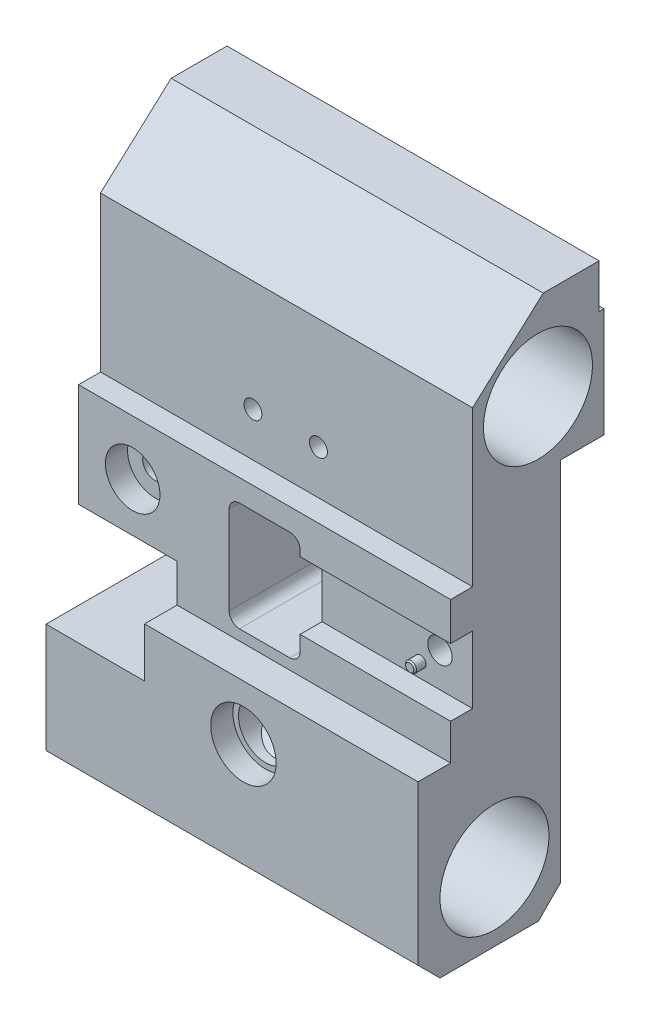
SolidWorks part; units mm, degrees
material "1060 Alloy"
ref_plane "Front Plane" through (0, 0, 0) normal (0, 0, 1) x (1, 0, 0)
ref_plane "Top Plane" through (0, 0, 0) normal (0, 1, 0) x (1, 0, 0)
ref_plane "Right Plane" through (0, 0, 0) normal (1, 0, 0) x (0, 0, -1)
sketch "Sketch1" plane through (0, 0, 0) normal (1, 0, 0) x (0, 0, -1)
  line L0 (14.15, 137.2) -> (30.37, 137.2)
  line L1 (30.37, 137.2) -> (30.37, 124.41)
  line L2 (30.37, 124.41) -> (31.79, 124.41)
  line L3 (31.79, 124.41) -> (31.79, 92.72)
  line L4 (31.79, 92.72) -> (19.1, 92.72)
  line L5 (19.1, 92.72) -> (19.1, -13.636)
  line L6 (19.1, -13.636) -> (12.736, -20)
  line L7 (12.736, -20) -> (-15.816, -20)
  line L8 (-15.816, -20) -> (-22.18, -13.636)
  line L9 (-22.18, -13.636) -> (-22.18, 32.5)
  line L10 (-22.18, 32.5) -> (-12.73, 32.5)
  line L11 (-12.73, 32.5) -> (-12.73, 73.61)
  line L12 (-12.73, 73.61) -> (-6.36, 73.61)
  line L13 (-6.36, 73.61) -> (-6.36, 118.61)
  line L14 (-6.36, 118.61) -> (14.15, 137.2)
  line L15 (-22.18, 32.5) -> (-22.18, 137.2) construction
  line L16 (-22.18, 137.2) -> (14.15, 137.2) construction
  line L17 (30.37, 137.2) -> (31.79, 137.2) construction
  line L18 (31.79, 137.2) -> (31.79, 124.41) construction
  line L19 (31.79, 92.72) -> (31.79, -20) construction
  line L20 (31.79, -20) -> (12.736, -20) construction
  line L21 (-22.18, -13.636) -> (-22.18, -20) construction
  line L22 (-22.18, -20) -> (-15.816, -20) construction
  line L23 (-22.18, 0) -> (31.79, 0) construction
  line L24 (0, -20) -> (0, 17.0401) construction
  line L25 (-22.18, -13.636) -> (19.1, -13.636) construction
  line L26 (0, -15.83) -> (46.0148, -15.83) construction
  line L27 (15.83, 0) -> (15.83, 26.825) construction
  line L28 (0, 15.83) -> (31.79, 15.83) construction
  line L29 (12.625, 111.985) -> (46.8932, 111.985) construction
  line L30 (12.625, 127.815) -> (56.5516, 127.815) construction
  line L31 (12.625, 96.155) -> (52.1782, 96.155) construction
  line L32 (30.37, 124.41) -> (30.37, 97.4751) construction
  line L33 (-15.83, 0) -> (-15.83, 21.2691) construction
  circle A0 centre (0, 0) radius 15.83
  circle A1 centre (12.625, 111.985) radius 15.83
  dimension "D19" = 111.985
  dimension "D14" = 31.66
  dimension "D1" = 41.28
  dimension "D2" = 38.15
  dimension "D3" = 157.2
  dimension "D4" = 44.48
  dimension "D5" = 1.42
  dimension "D6" = 31.69
  dimension "D7" = 25.46
  dimension "D8" = 31.83
  dimension "D9" = 52.5
  dimension "D10" = 93.61
  dimension "D11" = 9
  dimension "D12" = 12.625
  dimension "D13" = 16.22
  dimension "D15" = 45
  dimension "D16" = 3.27
  dimension "D17" = 6.35
  dimension "D18" = 4.17
extrude "Boss-Extrude1" add sketch "Sketch1" along normal blind 54 and the other way blind 54
sketch "Sketch2" plane through (0, 0, -19.1) normal (0, 0, -1) x (-1, 0, 0)
  line L0 (54, -13.636) -> (54, 92.72) construction
  line L1 (-7.3, 67.2) -> (7.3, 67.2)
  line L2 (-10.3, 64.2) -> (-10.3, 38.6)
  line L3 (-7.3, 35.6) -> (7.3, 35.6)
  line L4 (10.3, 64.2) -> (10.3, 38.6)
  line L5 (54, 43.53) -> (25.4, 43.53)
  line L6 (54, 43.53) -> (54, 18.13)
  line L7 (54, 18.13) -> (25.4, 18.13)
  line L8 (25.4, 43.53) -> (25.4, 18.13)
  line L9 (-9.25, 86.37) -> (9.75, 86.37) construction
  line L10 (-10.3, 64.2) -> (-10.3, 67.2) construction
  line L11 (-10.3, 67.2) -> (-7.3, 67.2) construction
  line L12 (7.3, 67.2) -> (10.3, 67.2) construction
  line L13 (10.3, 67.2) -> (10.3, 64.2) construction
  line L14 (10.3, 38.6) -> (10.3, 35.6) construction
  line L15 (10.3, 35.6) -> (7.3, 35.6) construction
  line L16 (-7.3, 35.6) -> (-10.3, 35.6) construction
  line L17 (-10.3, 35.6) -> (-10.3, 38.6) construction
  line L18 (-54, -13.636) -> (-54, 92.72) construction
  line L19 (54, -20) -> (-54, -20) construction
  line L21 (54, 137.2) -> (-54, 137.2) construction
  line L22 (-3.3, 16.595) -> (-3.3, 92.72) construction
  line L25 (54, 92.72) -> (-54, 92.72) construction
  line L26 (9.75, 86.37) -> (9.75, 92.72) construction
  line L27 (-9.25, 86.37) -> (-9.25, 92.72) construction
  line L28 (38.3, 57.72) -> (38.3, 92.72) construction
  line L29 (-44.55, 52.92) -> (-44.55, 92.72) construction
  circle A0 centre (-3.3, 16.595) radius 7.875
  circle A1 centre (-44.55, 52.92) radius 5.5 construction
  circle A2 centre (38.3, 57.72) radius 5.55 construction
  circle A3 centre (-9.25, 86.37) radius 2.6
  circle A4 centre (9.75, 86.37) radius 2.6
  circle A5 centre (-3.3, 16.595) radius 9.42 construction
  circle A6 centre (-9.25, 86.37) radius 4.425 construction
  circle A7 centre (9.75, 86.37) radius 4.425 construction
  circle A8 centre (38.3, 57.72) radius 3.525
  circle A9 centre (-44.55, 52.92) radius 3.55
  arc A10 (-7.3, 35.6) -> (-10.3, 38.6) centre (-7.3, 38.6) cw
  arc A11 (7.3, 35.6) -> (10.3, 38.6) centre (7.3, 38.6) ccw
  arc A12 (7.3, 67.2) -> (10.3, 64.2) centre (7.3, 64.2) cw
  arc A13 (-7.3, 67.2) -> (-10.3, 64.2) centre (-7.3, 64.2) ccw
  dimension "D1" = 3
  dimension "D17" = 18.84
  dimension "D18" = 15.75
  dimension "D20" = 8.85
  dimension "D21" = 5.2
  dimension "D22" = 7.05
  dimension "D23" = 11.1
  dimension "D24" = 7.1
  dimension "D25" = 11
  dimension "D2" = 43.7
  dimension "D3" = 43.7
  dimension "D4" = 55.6
  dimension "D5" = 70
  dimension "D6" = 38.13
  dimension "D7" = 25.4
  dimension "D8" = 28.6
  dimension "D9" = 15.7
  dimension "D10" = 44.25
  dimension "D11" = 63.25
  dimension "D12" = 9.45
  dimension "D13" = 50.7
  dimension "D14" = 35
  dimension "D15" = 6.35
  dimension "D16" = 39.8
  dimension "D19" = 76.125
extrude "Cut-Extrude1" cut sketch "Sketch2" against normal through all
sketch "Sketch3" plane through (0, 0, 12.73) normal (0, 0, 1) x (1, 0, 0)
  line L0 (54, 73.61) -> (54, 32.5) construction
  line L1 (54, 43) -> (10.3, 43)
  line L2 (54, 43) -> (54, 62.52)
  line L3 (54, 62.52) -> (10.3, 62.52)
  line L4 (10.3, 43) -> (10.3, 62.52)
  line L5 (10.3, 38.6) -> (10.3, 64.2) construction
  line L6 (-25.4, 32.5) -> (54, 32.5) construction
  dimension "D1" = 10.5
  dimension "D2" = 19.52
extrude "Cut-Extrude2" cut sketch "Sketch3" against normal blind 6.36
sketch "Sketch4" plane through (0, 0, 6.37) normal (0, 0, 1) x (1, 0, 0)
  line L0 (40.5, 47.335) -> (54, 47.335) construction
  line L2 (54, 43) -> (54, 62.52) construction
  line L3 (38.915, 48.92) -> (38.915, 62.52) construction
  line L4 (54, 62.52) -> (10.3, 62.52) construction
  circle A0 centre (38.915, 47.335) radius 1.585
  dimension "D1" = 3.17
  dimension "D2" = 13.5
  dimension "D3" = 13.6
extrude "Boss-Extrude2" add sketch "Sketch4" along normal blind 3.15
sketch "Sketch10" plane through (0, 0, -19.1) normal (0, 0, -1) x (-1, 0, 0)
  circle A1 centre (-38.915, 47.335) radius 1.585
  circle A2 centre (-38.915, 47.335) radius 1.585
  dimension "D1" = 0
extrude "Cut-Extrude6" cut sketch "Sketch10" against normal blind 20
sketch "Sketch11" plane through (0, 0, -19.1) normal (0, 0, -1) x (-1, 0, 0)
  circle A0 centre (38.3, 57.72) radius 5.5
  circle A1 centre (-44.55, 52.92) radius 5.42
  circle A2 centre (-9.25, 86.37) radius 4.55
  circle A3 centre (9.75, 86.37) radius 4.55
  circle M11 centre (38.3, 57.72) radius 3.525
  circle M12 centre (9.75, 86.37) radius 2.6
  circle M13 centre (-9.25, 86.37) radius 2.6
  dimension "D1" = 10.84
  dimension "D2" = 11
  dimension "D3" = 9.1
extrude "Cut-Extrude7" cut sketch "Sketch11" against normal blind 6.56 contours A0 M11 | A1 region at (-32.9556, 57.72, -19.1)
chamfer "Chamfer1" distance 0.4 angle 45 1 edges at (40.5, 47.335, 9.52)
sketch "Sketch5" plane through (0, 0, 12.73) normal (0, 0, 1) x (1, 0, 0)
  circle A0 centre (-38.3, 57.72) radius 7.925
  dimension "D1" = 15.85
extrude "Cut-Extrude3" cut sketch "Sketch5" against normal blind 6.44
sketch "Sketch6" plane through (0, 0, 22.18) normal (0, 0, 1) x (1, 0, 0)
  circle A0 centre (3.3, 16.595) radius 9.495
  dimension "D1" = 18.99
extrude "Cut-Extrude4" cut sketch "Sketch6" against normal blind 6.44
sketch "Sketch7" plane through (0, 0, -19.1) normal (0, 0, -1) x (-1, 0, 0)
  line L0 (25.4, 43.53) -> (25.4, 18.13) construction
  line L1 (25.4, 34.07) -> (16.63, 34.07)
  line L2 (25.4, 34.07) -> (25.4, -0.89)
  line L3 (25.4, -0.89) -> (16.63, -0.89)
  line L4 (16.63, 34.07) -> (16.63, -0.89)
  line L5 (54, 92.72) -> (-54, 92.72) construction
  dimension "D1" = 8.77
  dimension "D2" = 34.96
  dimension "D3" = 58.65
extrude "Boss-Extrude3" add sketch "Sketch7" along normal blind 3.1
sketch "Sketch8" plane through (0, 0, -22.2) normal (0, 0, -1) x (-1, 0, 0)
  line L0 (21.4, 3.82) -> (21.4, 92.72) construction
  line L1 (54, 92.72) -> (-54, 92.72) construction
  line L2 (16.63, -0.89) -> (25.4, -0.89) construction
  line L5 (25.4, -0.89) -> (25.4, 34.07) construction
  circle A0 centre (21.4, 29.135) radius 2
  circle A1 centre (21.4, 3.82) radius 2
  dimension "D2" = 4
  dimension "D1" = 4
  dimension "D3" = 4.71
  dimension "D4" = 30.025
extrude "Cut-Extrude5" cut sketch "Sketch8" against normal blind 15
extrude "Cut-Extrude8" cut sketch "Sketch11<3>" against normal blind 5.45 contours A2 M13 | A3 M12 region at (13.6713, 86.37, -19.1) region at (-5.3287, 86.37, -19.1)
sketch "Sketch11<3>" plane through (0, 0, -19.1) normal (0, 0, -1) x (-1, 0, 0) same geometry as "Sketch11"
sketch "Sketch12" plane through (0, 0, -19.1) normal (0, 0, -1) x (-1, 0, 0)
  circle A0 centre (-3.3, 16.595) radius 9.475
  dimension "D1" = 18.95
extrude "Cut-Extrude9" cut sketch "Sketch12" against normal blind 5.15
sketch "Sketch13" plane through (0, 0, -19.1) normal (0, 0, -1) x (-1, 0, 0)
  line L0 (-17.6348, 41.72) -> (20.3, 41.72) construction
  line L1 (-13.5, 41.72) -> (-13.5, 73.72) construction
  line L2 (13.2, 41.72) -> (13.2, 73.72) construction
  line L3 (-13.5, 73.72) -> (13.2, 73.72) construction
  line L4 (54, 92.72) -> (-54, 92.72) construction
  line L5 (-54, -13.636) -> (-54, 92.72) construction
  circle A0 centre (-13.5, 73.72) radius 2
  circle A1 centre (13.2, 73.72) radius 2
  circle A2 centre (-13.5, 41.72) radius 2
  circle A3 centre (13.2, 41.72) radius 2
  circle A4 centre (20.3, 41.72) radius 2
  circle A5 centre (-21, 41.92) radius 2
  circle A6 centre (21.4, 29.135) radius 2 construction
  dimension "D3" = 40.5
  dimension "D1" = 51
  dimension "D2" = 19
  dimension "D4" = 67.2
  dimension "D5" = 33
  dimension "D6" = 0.2
  dimension "D7" = 74.3
sketch "Sketch14" plane through (0, 0, -30.37) normal (0, 0, -1) x (-1, 0, 0)
  line L0 (-0.2, 130.91) -> (-0.2, 124.41) construction
  line L1 (54, 124.41) -> (-54, 124.41) construction
  line L2 (-0.2, 130.91) -> (-54, 130.91) construction
  line L3 (-54, 124.41) -> (-54, 137.2) construction
  circle A0 centre (-0.2, 130.91) radius 2
  circle A1 centre (13.2, 73.72) radius 2 construction
  dimension "D1" = 53.8
  dimension "D2" = 6.5
extrude "Cut-Extrude10" cut sketch "Sketch13" against normal blind 10
extrude "Cut-Extrude11" cut sketch "Sketch14" against normal blind 10
ref_axis "Axis1" through (-54, 111.985, -12.625) along (1, 0, 0)
ref_axis "Axis2" through (-54, 0, 0) along (1, 0, 0)
